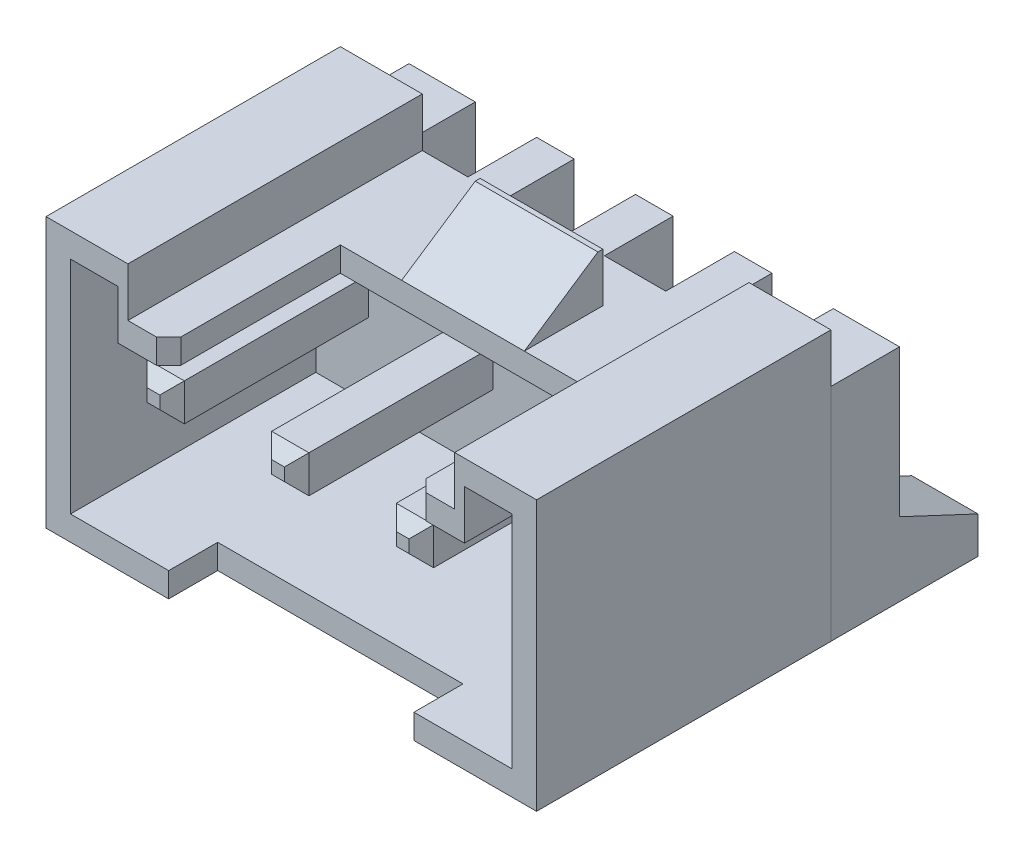
SolidWorks part; units mm, degrees
material "Nylon 101"
ref_plane "Plan de face" through (0, 0, 0) normal (0, 0, 1) x (1, 0, 0)
ref_plane "Plan de dessus" through (0, 0, 0) normal (0, 1, 0) x (1, 0, 0)
ref_plane "Plan de droite" through (0, 0, 0) normal (1, 0, 0) x (0, 0, -1)
sketch "Esquisse1" plane through (0, 0, 0) normal (0, 0, 1) x (1, 0, 0)
  line L0 (0, 7.0988) -> (0, -4.6394) construction
  line L1 (5, 0) -> (-5, 0)
  line L2 (-5, 0) -> (-5, 5.5)
  line L3 (-5, 5.5) -> (-3.33, 5.5)
  line L4 (-3.33, 5.5) -> (-3.33, 4.5)
  line L5 (-3.33, 4.5) -> (3.33, 4.5)
  line L6 (5, 0) -> (5, 5.5)
  line L7 (5, 5.5) -> (3.33, 5.5)
  line L8 (3.33, 5.5) -> (3.33, 4.5)
  line L9 (-4.5, 5) -> (-3.53, 5)
  line L10 (-3.53, 5) -> (-3.53, 4)
  line L11 (-3.53, 4) -> (3.53, 4)
  line L12 (3.53, 5) -> (3.53, 4)
  line L13 (4.5, 5) -> (3.53, 5)
  line L14 (4.5, 0.5) -> (4.5, 5)
  line L15 (4.5, 0.5) -> (-4.5, 0.5)
  line L16 (-4.5, 0.5) -> (-4.5, 5)
  line L17 (-3.83, 5) -> (-3.83, 4) construction
  line L18 (3.83, 5) -> (3.83, 4) construction
  line L19 (-4.5, 5) -> (-3.83, 5) construction
  line L20 (-3.83, 4) -> (3.83, 4) construction
  line L21 (4.5, 5) -> (3.83, 5) construction
  point P10 (0, 0)
  point P13 (0, 4.5)
  point P25 (3.33, 5)
  dimension "D1" = 5
  dimension "D2" = 1.67
  dimension "D3" = 1
  dimension "D4" = 5.5
  dimension "D6" = 0.2
  dimension "D7" = 0.2
  dimension "D5" = 0.5
extrude "Boss.-Extru.1" add sketch "Esquisse1" along normal blind 6
sketch "Esquisse2" plane through (0, 0, 0) normal (1, 0, 0) x (0, 0, -1)
  line L0 (-1, 5.5) -> (-2.5, 4.5)
  line L1 (-2.5, 4.5) -> (-0.9, 4.5)
  line L2 (-6, 4.5) -> (0, 4.5) construction
  line L3 (-6, 0) -> (-6, 5.5) construction
  line L5 (-6, 5.5) -> (0, 5.5) construction
  line L6 (-0.9, 4.5) -> (-0.9, 5.5)
  line L7 (-0.9, 5.5) -> (-1, 5.5)
  dimension "D1" = 1.6
  dimension "D2" = 0.1
  dimension "D3" = 3.5
extrude "Boss.-Extru.2" add sketch "Esquisse2" along normal blind 1.25 and the other way blind 1.25
sketch "Esquisse3" plane through (0, 0, 0) normal (0, 0, -1) x (-1, 0, 0)
  line L8 (-3.33, 5.5) -> (-5, 5.5)
  line L9 (-5, 5.5) -> (-5, 0)
  line L10 (-5, 0) -> (5, 0)
  line L11 (5, 0) -> (5, 5.5)
  line L12 (5, 5.5) -> (3.33, 5.5)
  line L13 (3.33, 5.5) -> (3.33, 4.5)
  line L14 (3.33, 4.5) -> (-3.33, 4.5)
  line L15 (-3.33, 4.5) -> (-3.33, 5.5)
  line L16 (-3.33, 5.5) -> (-5, 5.5)
  line L17 (-5, 5.5) -> (-5, 0)
  line L18 (-5, 0) -> (5, 0)
  line L19 (5, 0) -> (5, 5.5)
  line L20 (5, 5.5) -> (3.33, 5.5)
  line L21 (3.33, 5.5) -> (3.33, 4.5)
  line L22 (3.33, 4.5) -> (-3.33, 4.5)
  line L23 (-3.33, 4.5) -> (-3.33, 5.5)
  dimension "D1" = 0
extrude "Boss.-Extru.3" add sketch "Esquisse3" against normal blind 1
sketch "Esquisse4" plane through (0, 4.5, 0) normal (0, 1, 0) x (1, 0, 0)
  line L0 (-5, 0) -> (-5, 1.4)
  line L1 (-5, 1.4) -> (4.9985, 1.4)
  line L2 (4.9985, 1.4) -> (4.9985, 0)
  line L3 (-3.33, 0) -> (-5, 0) construction
  line L4 (4.9985, 0) -> (-5, 0)
  dimension "D1" = 9.9985
  dimension "D3" = 1.4
extrude "Boss.-Extru.4" add sketch "Esquisse4" against normal up to surface (4.5 mm away) up to face at (0, 0, 3)
sketch "Esquisse6" plane through (0, 0, -1.4) normal (0, 0, -1) x (-1, 0, 0)
  line L0 (-4.9985, 4.5) -> (5, 4.5) construction
  line L1 (-3.6485, 4.5) -> (-2.3985, 4.5)
  line L2 (-3.6485, 4.5) -> (-3.6485, 0)
  line L3 (-3.6485, 0) -> (-2.3985, 0)
  line L4 (-2.3985, 4.5) -> (-2.3985, 0)
  line L5 (5, 0) -> (-4.9985, 0) construction
  line L6 (0, -0.7198) -> (0, 6.3059) construction
  line L7 (-4.9985, 0) -> (-4.9985, 4.5) construction
  line L8 (1.6335, 0) -> (0.3835, 0)
  line L9 (-1.6335, 4.5) -> (-0.3835, 4.5)
  line L10 (-1.6335, 4.5) -> (-1.6335, 0)
  line L11 (-1.6335, 0) -> (-0.3835, 0)
  line L12 (-0.3835, 4.5) -> (-0.3835, 0)
  line L13 (0.3835, 4.5) -> (0.3835, 0)
  line L14 (1.6335, 4.5) -> (0.3835, 4.5)
  line L15 (1.6335, 4.5) -> (1.6335, 0)
  line L16 (3.6485, 0) -> (2.3985, 0)
  line L17 (2.3985, 4.5) -> (2.3985, 0)
  line L18 (3.6485, 4.5) -> (2.3985, 4.5)
  line L19 (3.6485, 4.5) -> (3.6485, 0)
  dimension "D1" = 1.25
  dimension "D2" = 1.35
  dimension "D3" = 0.765
  dimension "D4" = 1.25
extrude "Enlèv. mat.-Extru.1" cut sketch "Esquisse6" against normal blind 0.7
chamfer "Chanfrein1" distance 0.7 angle 45 4 edges at (-3.0235, 4.5, -0.7) (-1.0085, 4.5, -0.7) (1.0085, 4.5, -0.7) (3.0235, 4.5, -0.7)
sketch "Esquisse7" plane through (-5, 0, 0) normal (-1, 0, 0) x (0, 0, 1)
  line L0 (-1.4, 0) -> (-3, 0)
  line L1 (6, 5.5) -> (6, 0) construction
  line L2 (-1.4, 0) -> (-1.4, 4.5) construction
  line L3 (-1.4, 1.5) -> (-1.4, 0)
  line L4 (-3, 0) -> (-3, 0.75)
  line L5 (-3, 0.75) -> (-1.4, 1.5)
  dimension "D1" = 9
  dimension "D2" = 0.75
  dimension "D3" = 1.5
extrude "Boss.-Extru.5" add sketch "Esquisse7" against normal up to surface (1.3515 mm away) up to face at (-3.6485, 2.56, -0.84)
sketch "Esquisse8" plane through (4.9985, 0, 0) normal (1, 0, 0) x (0, 0, -1)
  line L1 (1.4, 0) -> (3, 0)
  line L2 (1.4, 0) -> (1.4, 1.5)
  line L3 (1.4, 1.5) -> (3, 0.75)
  line L9 (3, 0.75) -> (3, 0)
extrude "Boss.-Extru.6" add sketch "Esquisse8" against normal up to surface (1.35 mm away) up to face at (3.6485, 2.56, -0.84)
sketch "Esquisse9" plane through (0, 0, 1) normal (0, 0, 1) x (1, 0, 0)
  line L0 (0, -0.8536) -> (0, 6.2674) construction
  line L1 (-1.65, 2.76) -> (-0.89, 2.76)
  line L2 (-1.65, 2.76) -> (-1.65, 2)
  line L3 (-1.65, 2) -> (-0.89, 2)
  line L4 (-0.89, 2.76) -> (-0.89, 2)
  line L5 (4.5, 0.5) -> (-4.5, 0.5) construction
  line L6 (3.43, 2) -> (3.43, 2.76)
  line L7 (-3.43, 2) -> (-4.19, 2)
  line L8 (-3.43, 2) -> (-3.43, 2.76)
  line L9 (-3.43, 2.76) -> (-4.19, 2.76)
  line L10 (-4.19, 2) -> (-4.19, 2.76)
  line L11 (3.43, 2) -> (4.19, 2)
  line L12 (4.19, 2) -> (4.19, 2.76)
  line L13 (3.43, 2.76) -> (4.19, 2.76)
  line L14 (1.65, 2.76) -> (1.65, 2)
  line L15 (1.65, 2.76) -> (0.89, 2.76)
  line L16 (0.89, 2.76) -> (0.89, 2)
  line L17 (1.65, 2) -> (0.89, 2)
  dimension "D1" = 0.76
  dimension "D2" = 0.89
  dimension "D3" = 1.5
  dimension "D4" = 0.76
  dimension "D5" = 1.78
extrude "Boss.-Extru.7" add sketch "Esquisse9" along normal blind 4
chamfer "Chanfrein2" distance 0.25 angle 45 16 edges at (3.43, 2.38, 5) (3.81, 2.76, 5) (4.19, 2.38, 5) (3.81, 2, 5) (1.65, 2.38, 5) (1.27, 2, 5) (0.89, 2.38, 5) (1.27, 2.76, 5) (-1.27, 2.76, 5) (-0.89, 2.38, 5) (-1.27, 2, 5) (-1.65, 2.38, 5) (-3.81, 2, 5) (-4.19, 2.38, 5) (-3.81, 2.76, 5) (-3.43, 2.38, 5)
sketch "Esquisse10" plane through (0, 4.5, 0) normal (0, 1, 0) x (1, 0, 0)
  line L0 (0, 2.2567) -> (0, -7.0381) construction
  line L1 (-2.5, -2.5) -> (2.5, -2.5)
  line L2 (-2.5, -2.5) -> (-2.5, -6.25)
  line L3 (-2.5, -6.25) -> (2.5, -6.25)
  line L4 (2.5, -2.5) -> (2.5, -6.25)
  line L5 (3.33, -6) -> (-3.33, -6) construction
  dimension "D1" = 5
  dimension "D2" = 3.5
  dimension "D3" = 0.25
extrude "Enlèv. mat.-Extru.2" cut sketch "Esquisse10" against normal up to next
chamfer "Chanfrein3" distance 0.25 angle 45 2 edges at (2.5, 4.25, 6) (-2.5, 4.25, 6)
sketch "Esquisse11" plane through (0, 0.5, 0) normal (0, 1, 0) x (1, 0, 0)
  line L0 (0, 2.2121) -> (0, -7.0797) construction
  line L1 (-2.5, -6.25) -> (2.5, -6.25)
  line L2 (-2.5, -6.25) -> (-2.5, -5)
  line L3 (-2.5, -5) -> (2.5, -5)
  line L4 (2.5, -6.25) -> (2.5, -5)
  line L5 (-4.5, -6) -> (4.5, -6) construction
  dimension "D1" = 5
  dimension "D2" = 1
  dimension "D3" = 0.25
extrude "Enlèv. mat.-Extru.3" cut sketch "Esquisse11" against normal up to next
equation "\"3.53.00mm\"=3"
